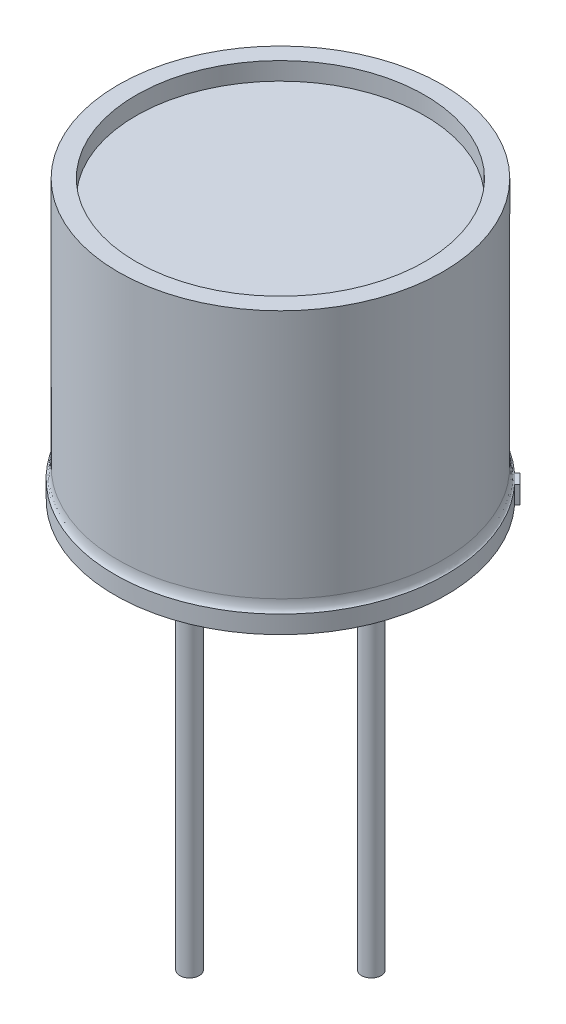
SolidWorks part; units mm, degrees
ref_plane "Front Plane" through (0, 0, 0) normal (0, 0, 1) x (1, 0, 0)
ref_plane "Top Plane" through (0, 0, 0) normal (0, 1, 0) x (1, 0, 0)
ref_plane "Right Plane" through (0, 0, 0) normal (1, 0, 0) x (0, 0, -1)
sketch "Sketch1" plane through (0, 0, 0) normal (0, 1, 0) x (1, 0, 0)
  circle A0 centre (0, 0) radius 4.55
  dimension "D1" = 9.1
extrude "Boss-Extrude1" add sketch "Sketch1" along normal blind 7.8
sketch "Sketch2" plane through (0, 7.8, 0) normal (0, 1, 0) x (1, 0, 0)
  circle A0 centre (0, 0) radius 4.05
extrude "Cut-Extrude1" cut sketch "Sketch2" against normal blind 0.5
sketch "Sketch3" plane through (0, 0, 0) normal (0, -1, 0) x (-1, 0, 0)
  circle A0 centre (0, 2.55) radius 0.275
  circle A1 centre (2.55, 0) radius 0.275
  circle A2 centre (0, -2.55) radius 0.275
  circle A3 centre (-2.55, 0) radius 0.275
  point P12 (0, 0)
  dimension "D2" = 0.55
  dimension "D1" = 2.55
  dimension "D3" = 4
extrude "Boss-Extrude2" add sketch "Sketch3" along normal blind 10.16
sketch "Sketch4" plane through (0, 0, 0) normal (0, -1, 0) x (-1, 0, 0)
  circle A0 centre (0, 0) radius 4.65
extrude "Boss-Extrude3" add sketch "Sketch4" against normal blind 0.5
fillet "Fillet1" radius 0.1 1 edges at (0, 0.5, -4.55) second distance 0.3 first distance on face at (0, 0.5, -4.55)
sketch "Sketch5" plane through (0, 0, 0) normal (0, -1, 0) x (-1, 0, 0)
  line L0 (0, 0) -> (-3.288, 3.288)
  line L6 (-3.0759, 3.3588) -> (-3.2173, 3.5002)
  line L7 (-3.2173, 3.5002) -> (-3.5002, 3.2173)
  line L8 (-3.5002, 3.2173) -> (-3.3588, 3.0759)
  line L9 (-3.3588, 3.0759) -> (-3.0759, 3.3588)
  circle A0 centre (0, 0) radius 4.65 construction
  point P8 (-3.288, 3.288)
  point P11 (-3.1466, 3.4295)
  dimension "D1" = 0.2
  dimension "D2" = 0
  dimension "D3" = 0.4
  dimension "D4" = 0.2
extrude "Boss-Extrude4" add sketch "Sketch5" against normal blind 0.5 contours L7 L8 L9 L6
